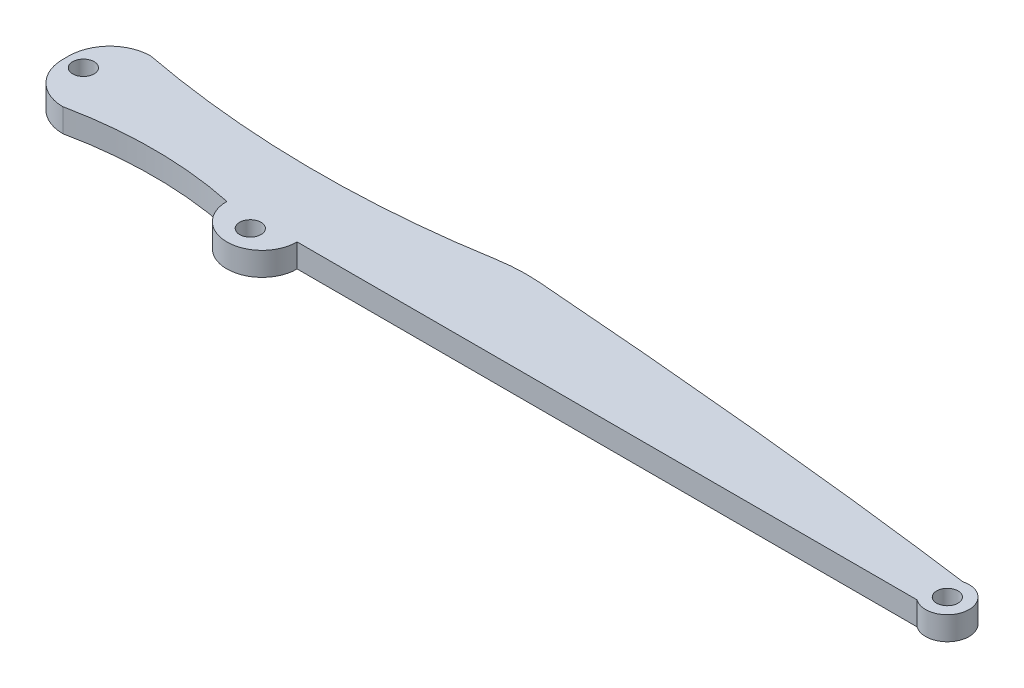
SolidWorks part; units mm, degrees
ref_plane "Front Plane" through (0, 0, 0) normal (0, 0, 1) x (1, 0, 0)
ref_plane "Top Plane" through (0, 0, 0) normal (0, 1, 0) x (1, 0, 0)
ref_plane "Right Plane" through (0, 0, 0) normal (1, 0, 0) x (0, 0, -1)
sketch "Sketch2" plane through (0, 0, 0) normal (0, 1, 0) x (1, 0, 0)
  line L11 (-78, 7.5) -> (80, 7.5)
  line L12 (-78, 7.5) -> (-78, -7.5)
  line L13 (-78, -7.5) -> (80, -7.5)
  line L14 (80, 7.5) -> (80, -7.5)
  dimension "D2" = 80
  dimension "D1" = 158
  dimension "D3" = 15
  dimension "D4" = 7.5
extrude "Boss-Extrude1" add sketch "Sketch2" along normal blind 4
sketch "Sketch4" plane through (0, 0, 0) normal (0, 1, 0) x (1, 0, 0)
  line L0 (-78, -7.5) -> (80, -7.5) construction
  line L1 (-43, -7.5) -> (-31, -7.5)
  arc A0 (-43, -7.5) -> (-31, -7.5) centre (-37, -7.5) ccw
  dimension "D1" = 6
  dimension "D2" = 35
  dimension "D3" = 12
extrude "Boss-Extrude2" add sketch "Sketch4" along normal up to surface (4 mm away) up to face at (1, 4, 0)
sketch "Sketch5" plane through (0, 4, 0) normal (0, 1, 0) x (1, 0, 0)
  line L0 (-78, -7.5) -> (-43, -7.5) construction
  line L1 (-78, 7.5) -> (-78, -7.5) construction
  line L2 (80, -7.5) -> (80, 7.5) construction
  line L3 (-31, -7.5) -> (80, -7.5) construction
  circle A0 centre (-75, 0) radius 1.825
  circle A1 centre (-37, -9.5) radius 1.825
  circle A2 centre (77, -4.5) radius 1.825
  arc A3 (-43, -7.5) -> (-31, -7.5) centre (-37, -7.5) ccw construction
  point P10 (-37, -13.5)
  dimension "D1" = 3.65
  dimension "D2" = 3.65
  dimension "D3" = 3.65
  dimension "D4" = 6
  dimension "D5" = 4
  dimension "D6" = 7.5
  dimension "D7" = 3
  dimension "D8" = 3
  dimension "D9" = 3
extrude "Cut-Extrude1" cut sketch "Sketch5" against normal through all
sketch "Sketch6" plane through (0, 4, 0) normal (0, 1, 0) x (1, 0, 0)
  line L2 (80, 7.5) -> (-8.2315, 7.5)
  line L3 (80, 7.5) -> (-78, 7.5) construction
  line L6 (-8.2315, 7.5) -> (14.2901, 5.8703) construction
  line L7 (14.2901, 5.8703) -> (49.5381, 2.8486) construction
  line L8 (49.5381, 2.8486) -> (69.508, -0.0694) construction
  line L9 (69.508, -0.0694) -> (80, -1.4494) construction
  line L10 (80, -7.5) -> (80, 7.5) construction
  line L11 (80, -1.4494) -> (80, 7.5)
  spline S0 degree 4 poles (-8.2315, 7.5) (14.2901, 5.8703) (49.5381, 2.8486) (69.508, -0.0694) (80, -1.4494) knots 0 0 0 0 0 1 1 1 1 1
  dimension "D1" = 88.6991
  dimension "D8" = 1.6297
  dimension "D2" = 88.2315
  dimension "D3" = 8.9494
  dimension "D4" = 10.5824
  dimension "D5" = 19.9699
  dimension "D6" = 22.5216
  dimension "D7" = 35.248
extrude "Cut-Extrude2" cut sketch "Sketch6" against normal through all
fillet "Fillet1" radius 7 2 edges at (-78, 2, -7.5) (-78, 2, 7.5)
fillet "Fillet2" radius 2 3 edges at (-8.2315, 2, -7.5) (80, 2, 7.5) (80, 2, 1.4494)
sketch "Sketch7" plane through (0, 4, 0) normal (0, 1, 0) x (1, 0, 0)
  line L0 (-71, -7.5) -> (-43, -7.5)
  line L1 (-71, -7.5) -> (-43, -7.5) construction
  line L2 (-71, 7.5) -> (-8.1594, 7.5)
  line L3 (-8.3038, 7.5) -> (-71, 7.5) construction
  arc A1 (-43, -7.5) -> (-71, -7.5) centre (-57, -74.1454) ccw
  arc A2 (-71, 7.5) -> (-8.1594, 7.5) centre (-39.5797, 172.1905) ccw
  point P9 (-8.1594, 7.4948)
  dimension "D1" = 167.6609
  dimension "D2" = 62.8406
  dimension "D3" = 68.1
extrude "Cut-Extrude3" cut sketch "Sketch7" against normal through all
sketch "Sketch8" plane through (0, 4, 0) normal (0, 1, 0) x (1, 0, 0)
  circle A0 centre (77, -4.5) radius 3.7056
  dimension "D1" = 7.4112
extrude "Boss-Extrude4" add sketch "Sketch8" against normal up to surface (4 mm away) up to face at (-75, 0, 1.825)
sketch "Sketch9" plane through (0, 4, 0) normal (0, 1, 0) x (1, 0, 0)
  circle A2 centre (77, -4.5) radius 1.825
  dimension "D1" = 3.65
extrude "Cut-Extrude4" cut sketch "Sketch9" against normal through all
fillet "Fillet3" radius 30 1 edges at (-8.1796, 2, -7.4961)
